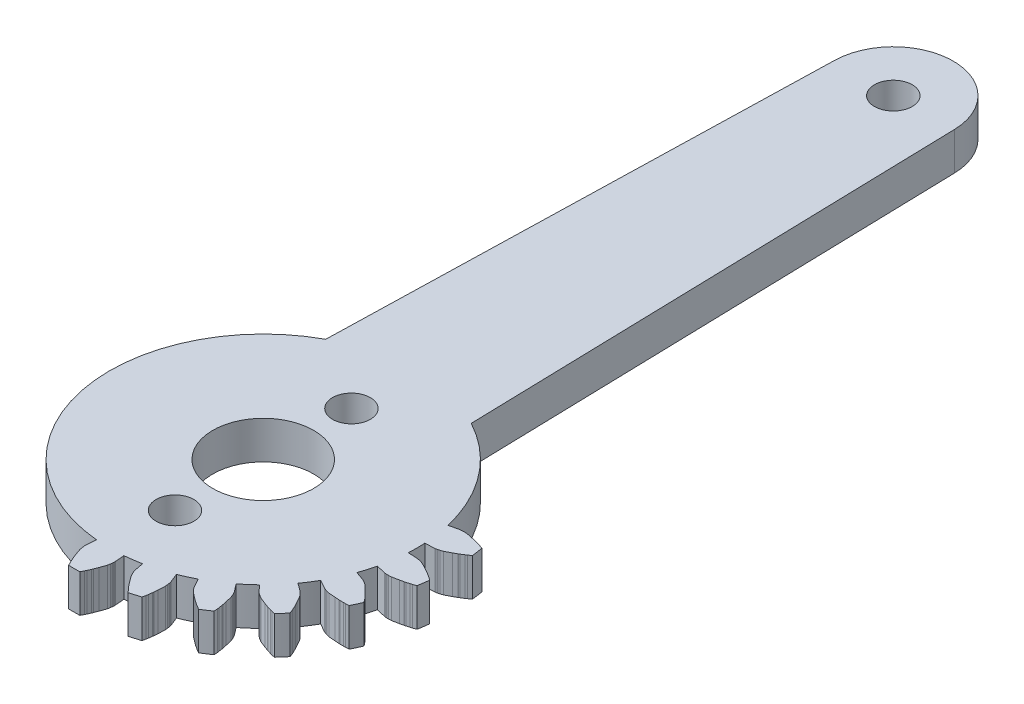
SolidWorks part; units mm, degrees
material "普通碳钢"
ref_plane "前视" through (0, 0, 0) normal (0, 0, 1) x (1, 0, 0)
ref_plane "上视" through (0, 0, 0) normal (0, 1, 0) x (1, 0, 0)
ref_plane "右视" through (0, 0, 0) normal (1, 0, 0) x (0, 0, -1)
sketch "草图1" plane through (0, 0, 0) normal (0, 1, 0) x (1, 0, 0)
  line L0 (39.751, 40.5224) -> (39.6866, 41.2679)
  line L1 (39.6866, 41.2679) -> (39.6851, 41.3287)
  line L2 (39.6851, 41.3287) -> (39.6859, 41.3577)
  line L3 (39.6859, 41.3577) -> (39.6916, 41.4528)
  line L4 (39.6916, 41.4528) -> (39.6929, 41.4698)
  line L5 (39.6929, 41.4698) -> (39.6966, 41.5042)
  line L6 (39.6966, 41.5042) -> (39.712, 41.6258)
  line L7 (39.712, 41.6258) -> (39.7121, 41.6267)
  line L8 (39.7121, 41.6267) -> (39.7482, 41.8247)
  line L9 (39.9295, 42.3366) -> (40.044, 42.6442)
  line L10 (40.044, 42.6442) -> (40.0454, 42.6478)
  line L11 (40.0454, 42.6478) -> (40.0855, 42.7398)
  line L12 (40.0855, 42.7398) -> (40.1995, 42.9971)
  line L13 (41.9203, 40.5224) -> (41.9848, 41.2679)
  line L14 (41.9848, 41.2679) -> (41.9862, 41.3287)
  line L15 (41.9862, 41.3287) -> (41.9855, 41.3577)
  line L16 (41.9855, 41.3577) -> (41.9797, 41.4528)
  line L17 (41.9797, 41.4528) -> (41.9784, 41.4698)
  line L18 (41.9784, 41.4698) -> (41.9748, 41.5042)
  line L19 (41.9748, 41.5042) -> (41.9594, 41.6258)
  line L20 (41.9594, 41.6258) -> (41.9592, 41.6267)
  line L21 (41.9592, 41.6267) -> (41.9231, 41.8247)
  line L22 (41.7419, 42.3366) -> (41.6274, 42.6442)
  line L23 (41.6274, 42.6442) -> (41.626, 42.6478)
  line L24 (41.626, 42.6478) -> (41.5858, 42.7398)
  line L25 (41.5858, 42.7398) -> (41.4718, 42.9971)
  circle A0 centre (40.8357, 28.3833) radius 12.1875 construction
  arc A1 (39.751, 40.5224) -> (41.9203, 40.5224) centre (40.8357, 28.3833) cw
  arc A2 (41.9231, 41.8247) -> (41.7419, 42.3366) centre (25.8953, 36.4382) ccw
  arc A4 (39.9295, 42.3366) -> (39.7482, 41.8247) centre (55.7761, 36.4382) ccw
  arc A5 (40.2653, 43.1347) -> (40.1995, 42.9971) centre (42.6892, 41.8899) ccw
  arc A6 (40.3945, 43.3768) -> (40.2653, 43.1347) centre (48.1168, 39.1026) ccw
  arc A11 (41.4718, 42.9971) -> (41.406, 43.1347) centre (38.9822, 41.8899) ccw
  arc A12 (41.406, 43.1347) -> (41.2769, 43.3768) centre (33.5546, 39.1026) ccw
  arc A13 (41.2769, 43.3768) -> (40.3945, 43.3768) centre (40.8357, 28.3833) ccw
  dimension "D1" = 24.375
extrude "凸台-拉伸1" add sketch "草图1" along normal blind 3 contours A4 L8 L7 L6 L5 L4 L3 L2 L1 L0 A1 L13 L14 L15 L16 L17 L18 L19 L20 L21 A2 L22 L23 L24 L25 A11 A12 A13 A6 A5 L12 L11 L10 L9
sketch "草图2" plane through (0, 0, 0) normal (0, -1, 0) x (1, 0, 0)
  circle A0 centre (40.8357, -28.3833) radius 12.1875
  circle A1 centre (40.8357, -28.3833) radius 4
  circle A2 centre (40.8357, -28.3833) radius 7 construction
  circle A3 centre (40.8357, -21.3833) radius 1.5
  circle A4 centre (40.8357, -35.3833) radius 1.5
  dimension "D1" = 8
  dimension "D2" = 24.375
  dimension "D3" = 14
  dimension "D4" = 3
  dimension "D5" = 3
extrude "凸台-拉伸2" add sketch "草图2" against normal blind 3
pattern_circular "阵列(圆周)2" count 22 over 360 about axis through (40.8357, 3, -28.3833) along (0, -1, 0) of "凸台-拉伸1"
sketch "草图3" plane through (0, 0, 0) normal (0, -1, 0) x (-1, 0, 0)
  circle A0 centre (-40.8357, 28.3833) radius 13.75
  dimension "D1" = 27.5
sketch "草图5" plane through (0, 0, 0) normal (0, -1, 0) x (1, 0, 0)
  line L0 (40.8357, -19.8833) -> (40.8357, -83.1349) construction
  line L1 (45.5857, -78.5069) -> (46.6107, -39.1157)
  line L2 (36.0857, -78.5069) -> (35.0607, -39.1157)
  circle A0 centre (40.8357, -21.3833) radius 1.5 construction
  circle A2 centre (40.8357, -28.3833) radius 12.1875 construction
  arc A3 (53.0056, -29.0373) -> (53.0056, -27.7293) centre (40.8357, -28.3833) ccw construction
  arc A4 (36.0857, -78.5069) -> (45.5857, -78.5069) centre (40.8357, -78.3833) ccw
  circle A5 centre (40.8357, -78.3833) radius 1.5
  arc A6 (35.0607, -39.1157) -> (46.6107, -39.1157) centre (40.8357, -28.3833) ccw
  dimension "D4" = 3
  dimension "D1" = 11.55
  dimension "D2" = 9.5
  dimension "D3" = 50
extrude "凸台-拉伸3" add sketch "草图5" against normal blind 3
sketch "草图7" plane through (0, 0, 0) normal (0, -1, 0) x (1, 0, 0)
  line L0 (36.0857, -78.5069) -> (35.0169, -37.4325) construction
  line L1 (35.0682, -39.4039) -> (36.0857, -78.5069) construction
  line L2 (45.5857, -78.5069) -> (46.6843, -36.2872) construction
  line L3 (45.5857, -78.5069) -> (46.6032, -39.4039) construction
  line L4 (35.0607, -39.1157) -> (35.0682, -39.4039)
  line L5 (35.0682, -39.4039) -> (34.8365, -39.8437)
  line L6 (34.8365, -39.8437) -> (33.6211, -45.0698)
  line L7 (33.6211, -45.0698) -> (23.2947, -35.4215)
  line L8 (23.2947, -35.4215) -> (25.1891, -22.1682)
  line L9 (25.1891, -22.1682) -> (31.4308, -11.204)
  line L10 (31.4308, -11.204) -> (37.9696, -9.817)
  line L11 (37.9696, -9.817) -> (39.751, -16.2441)
  line L12 (46.6107, -39.1157) -> (46.6032, -39.4039)
  line L13 (46.6032, -39.4039) -> (47.0142, -42.3632)
  line L14 (52.3284, -32.4394) -> (55.4375, -32.4394)
  line L15 (55.4375, -32.4394) -> (53.5277, -41.7128)
  line L16 (53.5277, -41.7128) -> (47.0142, -42.3632)
  arc A0 (35.0607, -39.1157) -> (39.751, -16.2441) centre (40.8357, -28.3833) cw
  circle A1 centre (40.8357, -28.3833) radius 4 construction
  circle A2 centre (40.8357, -28.3833) radius 12.1875 construction
  arc A3 (46.6107, -39.1157) -> (52.3284, -32.4394) centre (40.8357, -28.3833) ccw
extrude "切除-拉伸1" cut sketch "草图7" against normal blind 3
sketch "草图8" plane through (0, 0, 0) normal (0, -1, 0) x (1, 0, 0)
  line L0 (40.8357, -35.3833) -> (40.8357, -21.3833)
